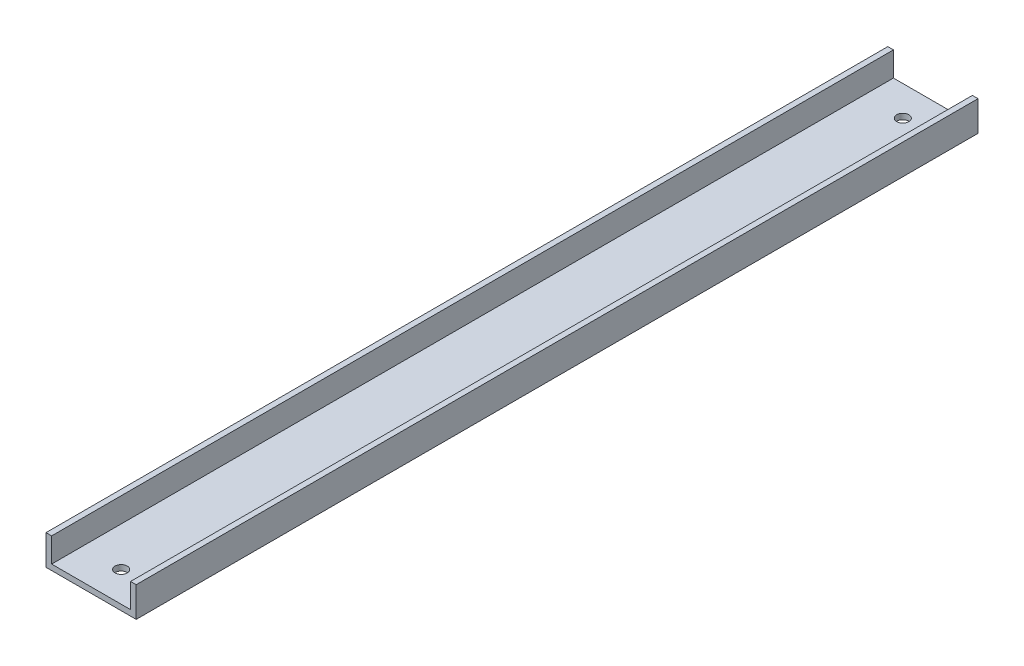
SolidWorks part; units mm, degrees
ref_plane "Front" through (0, 0, 0) normal (0, 0, 1) x (1, 0, 0)
ref_plane "Top" through (0, 0, 0) normal (0, 1, 0) x (1, 0, 0)
ref_plane "Right" through (0, 0, 0) normal (1, 0, 0) x (0, 0, -1)
sketch "Sketch1" plane through (0, 0, 0) normal (0, 0, 1) x (1, 0, 0)
  line L0 (-16.6688, 12.7) -> (-19.05, 12.7)
  line L1 (-19.05, 12.7) -> (-19.05, 0)
  line L2 (-19.05, 0) -> (19.05, 0)
  line L3 (19.05, 0) -> (19.05, 12.7)
  line L4 (19.05, 12.7) -> (16.6688, 12.7)
  line L5 (16.6688, 12.7) -> (16.6688, 2.3812)
  line L6 (16.6688, 2.3812) -> (-16.6688, 2.3812)
  line L7 (-16.6688, 2.3812) -> (-16.6688, 12.7)
  line L8 (0, 0) -> (0, 2.3813) construction
  line L9 (-16.6688, 12.7) -> (16.6688, 2.3812) construction
  line L10 (16.6688, 12.7) -> (-16.6688, 2.3812) construction
  point P11 (0, 7.5406)
  dimension "Outside Height" = 12.7
  dimension "Outside Width" = 38.1
  dimension "Wall Thickness" = 2.3813
sketch "Sketch2" plane through (0, 0, 0) normal (0, 0, 1) x (1, 0, 0)
  line L8 (-16.6688, 12.7) -> (-19.05, 12.7)
  line L9 (-19.05, 12.7) -> (-19.05, 0)
  line L10 (-19.05, 0) -> (19.05, 0)
  line L11 (19.05, 0) -> (19.05, 12.7)
  line L12 (19.05, 12.7) -> (16.6688, 12.7)
  line L13 (16.6688, 12.7) -> (16.6688, 2.3812)
  line L14 (16.6688, 2.3812) -> (-16.6688, 2.3812)
  line L15 (-16.6688, 2.3812) -> (-16.6688, 12.7)
  line L16 (-16.6688, 12.7) -> (-19.05, 12.7)
  line L17 (-19.05, 12.7) -> (-19.05, 0)
  line L18 (-19.05, 0) -> (19.05, 0)
  line L19 (19.05, 0) -> (19.05, 12.7)
  line L20 (19.05, 12.7) -> (16.6688, 12.7)
  line L21 (16.6688, 12.7) -> (16.6688, 2.3812)
  line L22 (16.6688, 2.3812) -> (-16.6688, 2.3812)
  line L23 (-16.6688, 2.3812) -> (-16.6688, 12.7)
  dimension "D1" = 0
extrude "Boss-Extrude1" add sketch "Sketch2" along normal mid plane 355.6
ref_axis "Center Axis 1" through (0, 7.5406, -19.3845) along (0, 0, 1)
ref_plane "Contact Plane 1" through (0, 0, 0) normal (0, -1, 0) x (-1, 0, 0)
hole_wizard "1/4-20 Tapped Hole1" positions "Sketch7" profile "Sketch8" tap size "1/4-20" standard "ANSI Inch" end condition through all
sketch "Sketch7" plane through (0, 2.3812, 0) normal (0, 1, 0) x (1, 0, 0)
  line L0 (16.6688, -177.8) -> (-16.6688, -177.8) construction
  point P0 (0, -165.1)
  point P5 (0, -177.8)
  dimension "D1" = 12.7
sketch "Sketch8" plane through (0, 2.3812, 165.1) normal (1, 0, 0) x (0, 0, 1)
  line L0 (0, 0) -> (0, 2.3813)
  line L1 (0, 2.3813) -> (2.5527, 2.3812)
  line L2 (2.5527, 2.3812) -> (2.5527, 0)
  line L5 (2.5527, 0) -> (0, 0)
  line L11 (0, -6.35) -> (0, 107.95) construction
  dimension "Thread Major Dia." = 5.1054
  dimension "Thru Tap Drill Depth" = 2.3812
mirror "Mirror1" about plane through (0, 0, 0) normal (0, 0, 1) of "1/4-20 Tapped Hole1"
